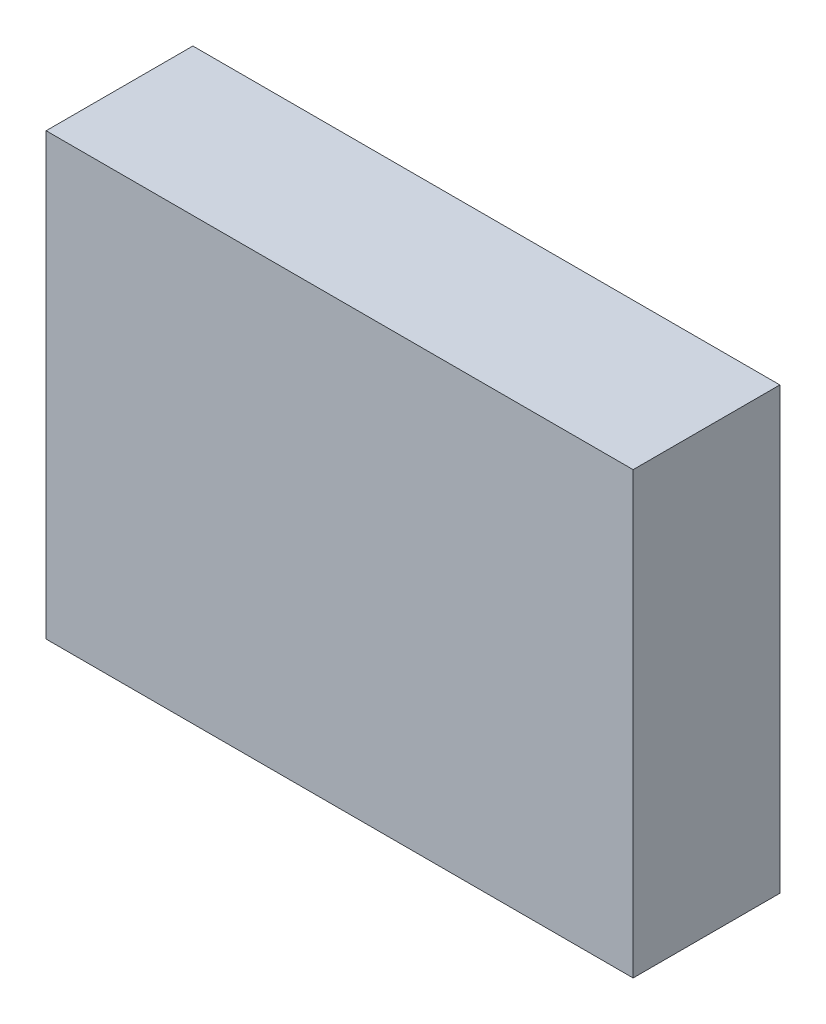
SolidWorks part; units mm, degrees
material "Cast Alloy Steel"
ref_plane "Front Plane" through (0, 0, 0) normal (1, 0, 0) x (0, 1, 0)
ref_plane "Top Plane" through (0, 0, 0) normal (0, 0, 1) x (0, 1, 0)
ref_plane "Right Plane" through (0, 0, 0) normal (0, 1, 0) x (-1, 0, 0)
sketch "Sketch1" plane through (0, 0, 0) normal (1, 0, 0) x (0, 1, 0)
  line L1 (0, -55) -> (0, 55) construction
  line L2 (-450, 150) -> (0, 150)
  line L3 (-450, 150) -> (-450, 0)
  line L4 (-450, 0) -> (0, 0)
  line L5 (0, 150) -> (0, 0)
  line L6 (0, 150) -> (150, 150)
  line L7 (0, 150) -> (0, 1150)
  line L8 (0, 1150) -> (150, 1150)
  line L9 (150, 150) -> (150, 1150)
  line L10 (-450, 0) -> (-600, 0)
  line L11 (-450, 0) -> (-450, -500)
  line L12 (-450, -500) -> (-600, -500)
  line L13 (-600, 0) -> (-600, -500)
  line L14 (55, 0) -> (-55, 0) construction
  dimension "D1" = 1000
  dimension "D2" = 150
  dimension "D3" = 150
  dimension "D4" = 150
  dimension "D5" = 450
  dimension "D6" = 500
  dimension "D7" = 0
  dimension "D8" = 0
extrude "Boss-Extrude2" add sketch "Sketch1" along normal blind 300 and the other way blind 300 contours L5 L2 L3 L4 region at (0, -225, 75)
sketch "Sketch2" plane through (0, 0, 0) normal (0, 0, -1) x (1, 0, 0)
  line L1 (-37.5, 145) -> (37.5, 145)
  line L2 (-37.5, 145) -> (-37.5, 305)
  line L3 (-37.5, 305) -> (37.5, 305)
  line L4 (-300, 0) -> (300, 0)
  line L5 (300, 0) -> (300, 450)
  line L6 (300, 450) -> (-300, 450)
  line L7 (-300, 450) -> (-300, 0)
  line L8 (-300, 0) -> (300, 0)
  line L9 (300, 0) -> (300, 450)
  line L10 (300, 450) -> (-300, 450)
  line L11 (-300, 450) -> (-300, 0)
  line L12 (37.5, 145) -> (37.5, 305)
  point P8 (0, 450)
  point P9 (0, 145)
  point P10 (-37.5, 225)
  point P11 (-300, 225)
  point P13 (-37.5, 305)
  point P14 (-37.5, 145)
  point P15 (37.5, 305)
  point P16 (37.5, 145)
  dimension "D2" = 0
  dimension "D3" = 0
  dimension "D4" = 75
  dimension "D5" = 160
  dimension "D1" = 0
hole_wizard "Ø2.0mm Dowel Hole1" positions "Sketch2" profile "Sketch4" hole size "Ø2.0" standard "IS"
sketch "Sketch4" plane through (37.5, -145, 0) normal (1, 0, 0) x (0, 1, 0)
  line L0 (0, 0) -> (0, 10.6009)
  line L1 (0, 10.6009) -> (1, 10)
  line L2 (1, 10) -> (1, 0.025)
  line L3 (1, 0.025) -> (1.025, 0)
  line L5 (1.025, 0) -> (0, 0)
  line L6 (-1, 0.025) -> (-1.025, 0) construction
  line L10 (0, 10.6009) -> (-1, 10) construction
  line L11 (0, -6.35) -> (0, 107.95) construction
  dimension "Hole Dia." = 2
  dimension "Hole Depth" = 10
  dimension "Near C'Sink Dia." = 2.05
  dimension "Near C'Sink Angle" = 90
  dimension "Drill Angle" = 118
sketch "Sketch5" plane through (0, 0, 0) normal (0, 0, -1) x (1, 0, 0)
  line L1 (-15, 87.5) -> (15, 87.5)
  line L2 (-15, 87.5) -> (-15, 12.5)
  line L3 (-15, 12.5) -> (15, 12.5)
  line L4 (-300, 0) -> (300, 0)
  line L5 (300, 0) -> (300, 450)
  line L6 (300, 450) -> (-300, 450)
  line L7 (-300, 450) -> (-300, 0)
  line L8 (-300, 0) -> (300, 0)
  line L9 (300, 0) -> (300, 450)
  line L10 (300, 450) -> (-300, 450)
  line L11 (-300, 450) -> (-300, 0)
  line L12 (15, 87.5) -> (15, 12.5)
  point P8 (0, 87.5)
  point P9 (0, 450)
  point P10 (15, 50)
  point P11 (300, 225)
  point P13 (-15, 87.5)
  point P14 (15, 87.5)
  point P15 (15, 12.5)
  point P16 (-15, 12.5)
  dimension "D2" = 0
  dimension "D3" = 30
  dimension "D4" = 75
  dimension "D5" = 175
  dimension "D1" = 0
hole_wizard "Ø2.0mm Dowel Hole2" positions "Sketch5" profile "Sketch6" hole size "Ø2.0" standard "IS"
sketch "Sketch6" plane through (-15, -12.5, 0) normal (1, 0, 0) x (0, 1, 0)
  line L0 (0, 0) -> (0, 10.6009)
  line L1 (0, 10.6009) -> (1, 10)
  line L2 (1, 10) -> (1, 0.025)
  line L3 (1, 0.025) -> (1.025, 0)
  line L5 (1.025, 0) -> (0, 0)
  line L6 (-1, 0.025) -> (-1.025, 0) construction
  line L10 (0, 10.6009) -> (-1, 10) construction
  line L11 (0, -6.35) -> (0, 107.95) construction
  dimension "Hole Dia." = 2
  dimension "Hole Depth" = 10
  dimension "Near C'Sink Dia." = 2.05
  dimension "Near C'Sink Angle" = 90
  dimension "Drill Angle" = 118
